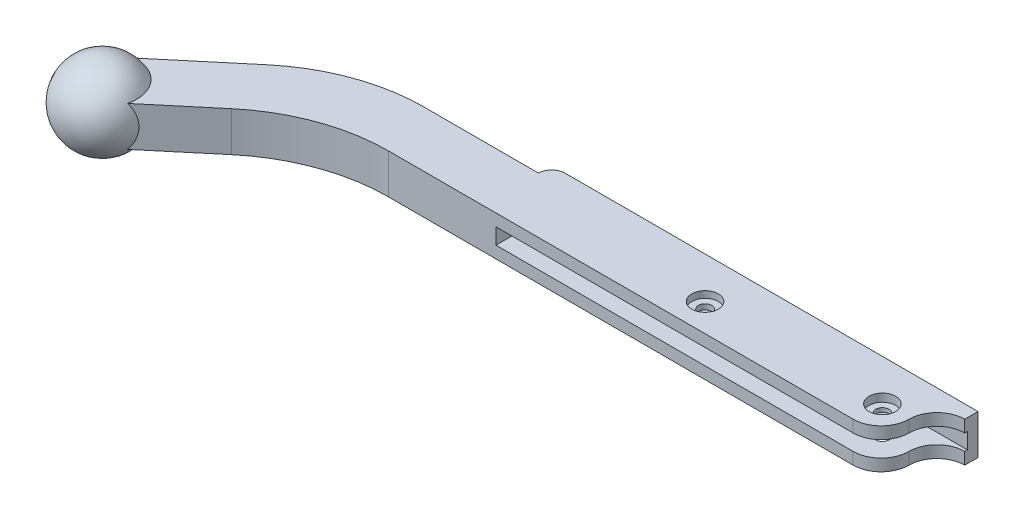
SolidWorks part; units mm, degrees
ref_plane "前视基准面" through (0, 0, 0) normal (0, 0, 1) x (1, 0, 0)
ref_plane "上视基准面" through (0, 0, 0) normal (0, 1, 0) x (1, 0, 0)
ref_plane "右视基准面" through (0, 0, 0) normal (1, 0, 0) x (0, 0, -1)
sketch "草图1" plane through (0, 0, 0) normal (0, 1, 0) x (1, 0, 0)
  line L1 (-107.5292, 13.1553) -> (42.4708, 13.1553)
  line L2 (-107.5292, 13.1553) -> (-107.5292, -7.8447)
  line L3 (-107.5292, -7.8447) -> (42.4708, -7.8447)
  line L4 (42.4708, 13.1553) -> (42.4708, -7.8447)
  dimension "D1" = 150
  dimension "D2" = 21
extrude "凸台-拉伸1" add sketch "草图1" along normal blind 15
sketch "草图2" plane through (42.4708, 0, 0) normal (1, 0, 0) x (0, 0, -1)
  line L0 (-7.8447, 15) -> (-7.8447, 0) construction
  line L1 (-7.8447, 10.5) -> (13.1553, 10.5)
  line L2 (-7.8447, 10.5) -> (-7.8447, 4.5)
  line L3 (-7.8447, 4.5) -> (13.1553, 4.5)
  line L4 (13.1553, 10.5) -> (13.1553, 4.5)
  line L5 (13.1553, 15) -> (13.1553, 0) construction
  line L6 (-7.8447, 15) -> (13.1553, 15) construction
  line L7 (-7.8447, 0) -> (13.1553, 0) construction
  dimension "D1" = 4.5
  dimension "D2" = 4.5
extrude "切除-拉伸1" cut sketch "草图2" against normal blind 145
sketch "草图3" plane through (0, 15, 0) normal (0, 1, 0) x (1, 0, 0)
  line L0 (42.4708, -7.8447) -> (42.4708, 13.1553) construction
  line L1 (42.4708, 13.1553) -> (-107.5292, 13.1553) construction
  circle A0 centre (32.4708, 2.6553) radius 5
  dimension "D1" = 10
  dimension "D2" = 10.5
extrude "切除-拉伸2" cut sketch "草图3" against normal blind 3
sketch "草图4" plane through (0, 0, 0) normal (0, -1, 0) x (-1, 0, 0)
  line L0 (-42.4708, -7.8447) -> (-42.4708, 13.1553) construction
  line L1 (107.5292, -7.8447) -> (-42.4708, -7.8447) construction
  circle A0 centre (-32.4708, 2.6553) radius 5
  dimension "D1" = 10
  dimension "D2" = 10.5
extrude "切除-拉伸3" cut sketch "草图4" against normal blind 3
sketch "草图5" plane through (0, 3, 0) normal (0, -1, 0) x (-1, 0, 0)
  circle A0 centre (-32.4708, 2.6553) radius 2.5
  circle A1 centre (-32.4708, 2.6553) radius 5 construction
  dimension "D1" = 0
extrude "切除-拉伸4" cut sketch "草图5" against normal blind 20
sketch "草图6" plane through (0, 15, 0) normal (0, 1, 0) x (1, 0, 0)
  line L0 (42.4708, 13.1553) -> (-107.5292, 13.1553) construction
  circle A0 centre (-34.2955, 2.6553) radius 5
  circle A1 centre (32.4708, 2.6553) radius 2.5 construction
  dimension "D1" = 10.5
  dimension "D2" = 66.7663
extrude "切除-拉伸5" cut sketch "草图6" against normal blind 20
sketch "草图7" plane through (0, 4.5, 0) normal (0, 1, 0) x (1, 0, 0)
  circle A0 centre (-34.2955, 2.6553) radius 6
  circle A2 centre (-34.2955, 2.6553) radius 5 construction
  dimension "D1" = 0
extrude "凸台-拉伸2" add sketch "草图7" against normal blind 2
sketch "草图8" plane through (0, 10.5, 0) normal (0, -1, 0) x (-1, 0, 0)
  circle A0 centre (34.2955, 2.6553) radius 6
  circle A1 centre (34.2955, 2.6553) radius 5 construction
  dimension "D1" = 0
extrude "凸台-拉伸3" add sketch "草图8" against normal blind 2
sketch "草图9" plane through (0, 12.5, 0) normal (0, 1, 0) x (1, 0, 0)
  circle A0 centre (-34.2955, 2.6553) radius 2.5
  circle A2 centre (-34.2955, 2.6553) radius 5 construction
  dimension "D1" = 0
extrude "切除-拉伸6" cut sketch "草图9" against normal blind 20
sketch "草图12" plane through (0, 15, 0) normal (0, 1, 0) x (1, 0, 0)
  line L0 (-107.5292, -7.8447) -> (-167.5292, -7.8447)
  line L1 (-167.5292, -7.8447) -> (-213.4919, -46.412)
  line L2 (-107.5292, 13.1553) -> (-175.1726, 13.1553)
  line L3 (-213.4919, -46.412) -> (-226.9904, -30.3251)
  line L4 (-226.9904, -30.3251) -> (-175.1726, 13.1553)
  line L5 (-107.5292, 13.1553) -> (-107.5292, -7.8447)
  dimension "D1" = 60
  dimension "D2" = 140
  dimension "D3" = 21
  dimension "D4" = 90
  dimension "D5" = 60
extrude "凸台-拉伸5" add sketch "草图12" against normal blind 15 separate body
sketch "草图13" plane through (-148.1356, 0, 124.3005) normal (-0.766, 0, 0.6428) x (0.6428, 0, 0.766)
  line L0 (-122.6763, 7.5) -> (-101.6763, 7.5) construction
  line L1 (-122.6763, 0) -> (-122.6763, 15) construction
  line L2 (-101.6763, 0) -> (-101.6763, 15) construction
  line L3 (-112.1763, 15) -> (-112.1763, 7.5) construction
  line L4 (-122.6763, 15) -> (-101.6763, 15) construction
  line L5 (-112.1763, 7.5) -> (-112.1763, 0) construction
  line L6 (-122.6763, 0) -> (-101.6763, 0) construction
  line L7 (-112.1763, 22.5) -> (-112.1763, -7.5)
  arc A0 (-112.1763, -7.5) -> (-112.1763, 22.5) centre (-112.1763, 7.5) ccw
revolve "旋转3" add sketch "草图13" angle 360 about L7
sketch "草图14" plane through (0, 0, -13.1553) normal (0, 0, -1) x (-1, 0, 0)
  line L1 (107.5292, 15) -> (-52.9708, 15)
  line L2 (107.5292, 15) -> (107.5292, 0)
  line L3 (107.5292, 0) -> (-52.9708, 0)
  line L4 (-52.9708, 15) -> (-52.9708, 0)
  dimension "D1" = 160.5
extrude "凸台-拉伸6" add sketch "草图14" along normal blind 5
fillet "圆角1" radius 5 1 edges at (-107.5292, 7.5, -18.1553)
fillet "圆角2" radius 10.5 4 edges at (42.4708, 2.25, 7.8447) (42.4708, 2.25, -13.1553) (42.4708, 12.75, 7.8447) (42.4708, 12.75, -13.1553)
fillet "圆角3" radius 67.5 2 edges at (-167.5292, 7.5, 7.8447) (-175.1726, 7.5, -13.1553)
sketch "草图15" plane through (0, 10.5, 0) normal (0, -1, 0) x (-1, 0, 0)
  point P0 (-32.4708, 2.6553)
ref_point "点2"
sketch "草图17" plane through (-102.5292, 0, 0) normal (1, 0, 0) x (0, 0, -1)
  line L0 (13.1553, 10.5) -> (13.1553, 4.5) construction
  line L1 (-7.8447, 10.5) -> (14.1553, 10.5)
  line L2 (-7.8447, 10.5) -> (-7.8447, 4.5)
  line L3 (-7.8447, 4.5) -> (14.1553, 4.5)
  line L4 (14.1553, 10.5) -> (14.1553, 4.5)
  dimension "D1" = 1
extrude "切除-拉伸7" cut sketch "草图17" along normal blind 200
